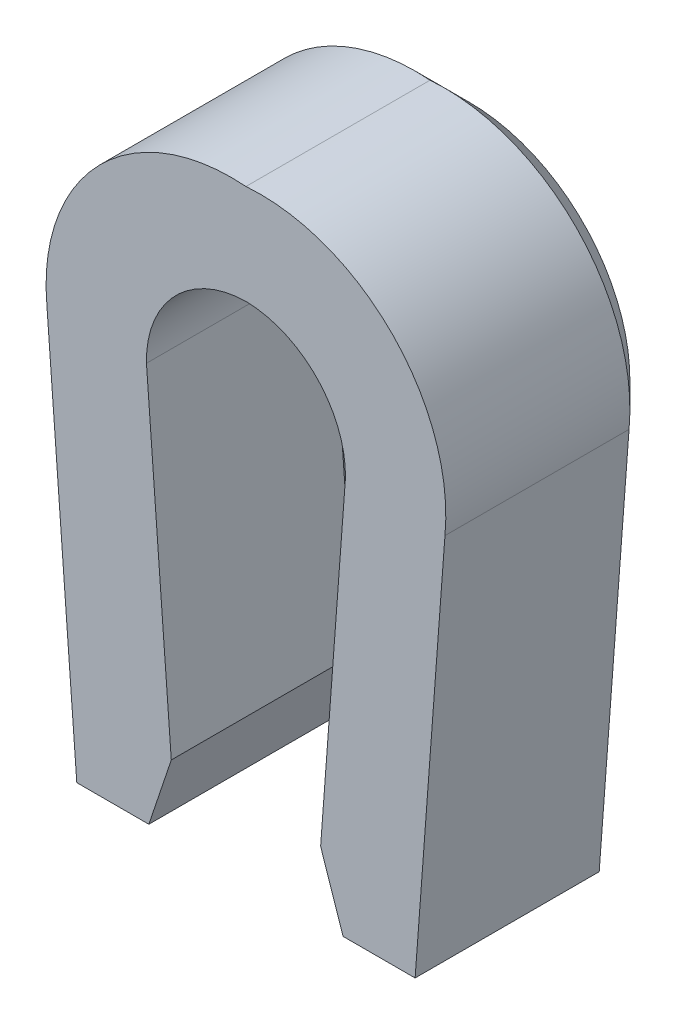
SolidWorks part; units mm, degrees
ref_plane "Front Plane" through (0, 0, 0) normal (0, 0, 1) x (1, 0, 0)
ref_plane "Top Plane" through (0, 0, 0) normal (0, 1, 0) x (1, 0, 0)
ref_plane "Right Plane" through (0, 0, 0) normal (1, 0, 0) x (0, 0, -1)
sketch "Sketch1" plane through (0, 0, 0) normal (0, 0, 1) x (1, 0, 0)
  line L0 (-2, 4) -> (-1.4, -4)
  line L5 (-1.4, -4) -> (-3.4, -4)
  line L6 (-3.4, -4) -> (-4, 4)
  line L10 (0, 7.8443) -> (0, -6.8113) construction
  line L11 (3.4, -4) -> (4, 4)
  line L12 (1.4, -4) -> (3.4, -4)
  line L13 (2, 4) -> (1.4, -4)
  arc A4 (-2, 4) -> (0, 6.0772) centre (0.036, 4.0411) cw
  arc A5 (-4, 4) -> (0, 8.0772) centre (-0.2889, 4.3599) cw
  arc A6 (4, 4) -> (0, 8.0772) centre (0.2889, 4.3599) ccw
  arc A7 (2, 4) -> (0, 6.0772) centre (-0.036, 4.0411) ccw
  dimension "D1" = 8
  dimension "D2" = 2
  dimension "D3" = 2
  dimension "D4" = 2
  dimension "D6" = 1.4
extrude "Boss-Extrude1" add sketch "Sketch1" along normal blind 4.2
sketch "Sketch2" plane through (0, 0, 0) normal (0, 0, 1) x (1, 0, 0)
  line L0 (-1.4, -4) -> (-1.9514, -4)
  line L1 (-3.4, -4) -> (-1.4, -4) construction
  line L2 (-1.9514, -4) -> (-1.5008, -2.6555)
  line L3 (-1.4, -4) -> (-2, 4) construction
  line L4 (-1.5008, -2.6555) -> (-1.4, -4)
  line L5 (1.4, -4) -> (1.5008, -2.6555)
  line L6 (2, 4) -> (1.4, -4) construction
  line L7 (1.5008, -2.6555) -> (1.9514, -4)
  line L8 (1.4, -4) -> (3.4, -4) construction
  line L9 (1.9514, -4) -> (1.4, -4)
extrude "Cut-Extrude2" cut sketch "Sketch2" along normal through all both and the other way through all
chamfer "Chamfer1" distance 0.5 angle 45 12 edges at (-1.431, 5.4536, 0) (1.431, 5.4536, 0) (2.6757, -4, 0) (3.7, 0, 0) (2.9504, 6.971, 0) (-2.9504, 6.971, 0) (-3.7, 0, 0) (-2.6757, -4, 0)
equation "\"thiccness\"=3.9"
equation "\"D1@Boss-Extrude1\"=\"thiccness\""
